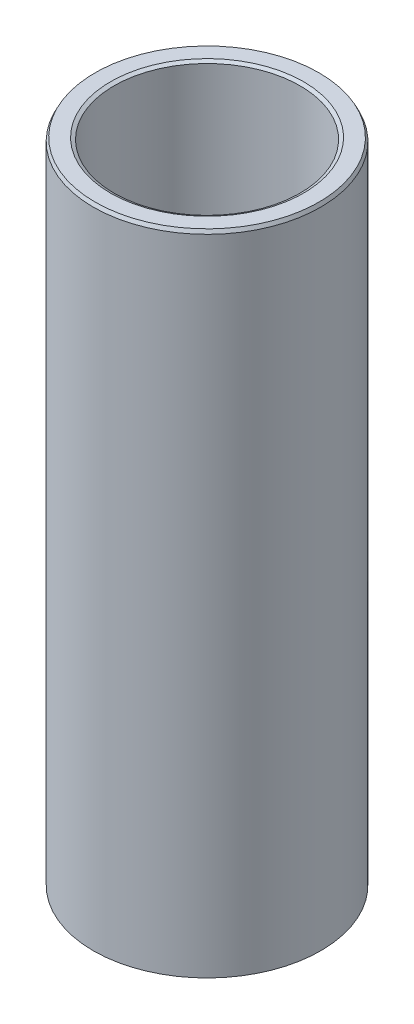
SolidWorks part; units mm, degrees
ref_plane "Front Plane" through (0, 0, 0) normal (0, 0, 1) x (1, 0, 0)
ref_plane "Top Plane" through (0, 0, 0) normal (0, 1, 0) x (1, 0, 0)
ref_plane "Right Plane" through (0, 0, 0) normal (1, 0, 0) x (0, 0, -1)
sketch "Sketch1" plane through (0, 0, 0) normal (0, 1, 0) x (1, 0, 0)
  circle A0 centre (0, 0) radius 37.5
  dimension "SLEEVE_OD" = 75
extrude "Boss-Extrude1" add sketch "Sketch1" along normal blind 214.0185
sketch "Sketch2" plane through (0, 0, 0) normal (0, 1, 0) x (1, 0, 0)
  circle A0 centre (0, 0) radius 30.6694
  dimension "BORE_D" = 61.3389
extrude "Cut-Extrude1" cut sketch "Sketch2" along normal through all
chamfer "Chamfer1" distance 1.1549 angle 26.843 4 edges at (0, 214.0185, 30.6694) (0, 0, 30.6694) (0, 0, 37.5) (0, 214.0185, 37.5) first distance on face at (0, 214.0185, 30.6694) first distance on face at (0, 0, 30.6694) first distance on face at (0, 214.0185, 37.5)
